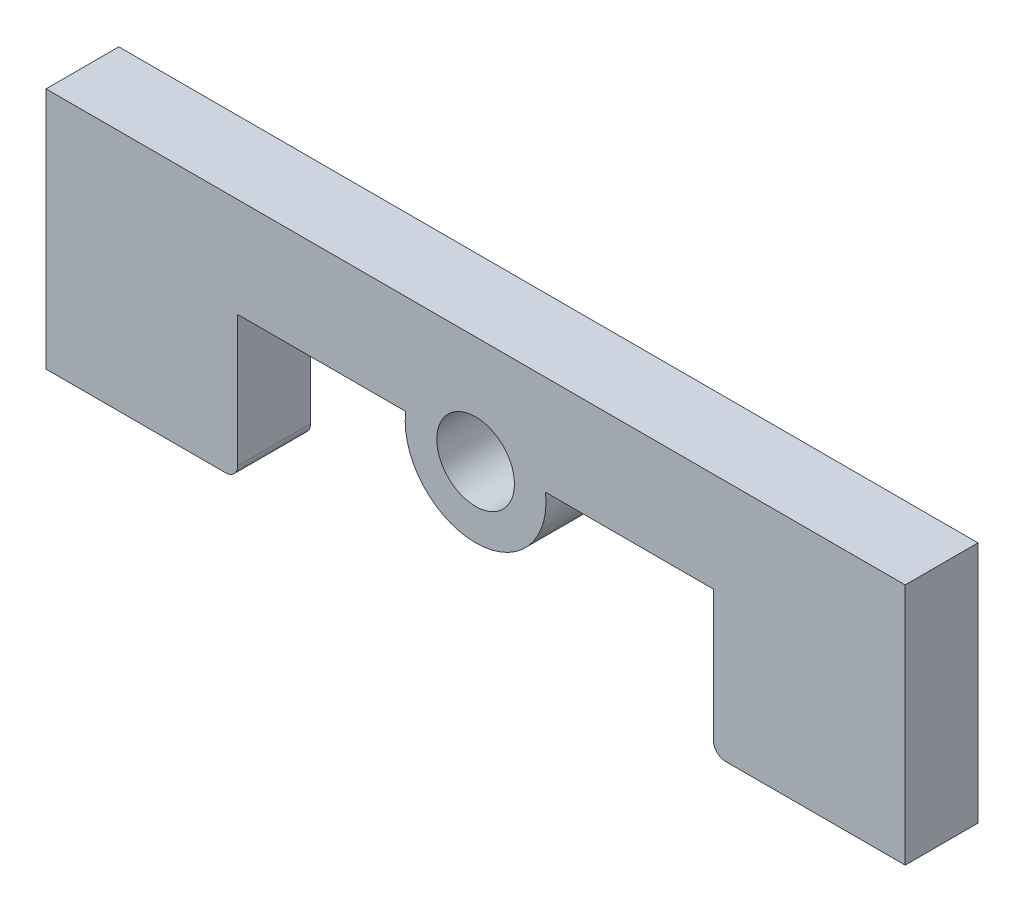
SolidWorks part; units mm, degrees
ref_plane "Front Plane" through (0, 0, 0) normal (0, 0, 1) x (1, 0, 0)
ref_plane "Top Plane" through (0, 0, 0) normal (0, 1, 0) x (1, 0, 0)
ref_plane "Right Plane" through (0, 0, 0) normal (1, 0, 0) x (0, 0, -1)
sketch "Sketch2" plane through (0, 0, 0) normal (0, 0, 1) x (1, 0, 0)
  line L0 (9.8, -5) -> (17.7, -5)
  line L1 (-17.7, -5) -> (-9.8, -5)
  line L2 (-17.7, -5) -> (-17.7, 5)
  line L3 (-17.7, 5) -> (17.7, 5)
  line L4 (17.7, -5) -> (17.7, 5)
  line L5 (-17.7, -5) -> (17.7, 5) construction
  line L6 (-17.7, 5) -> (17.7, -5) construction
  line L8 (-9.8, -5) -> (-9.8, 0.9)
  line L9 (-9.8, 0.9) -> (9.8, 0.9)
  line L10 (9.8, -5) -> (9.8, 0.9)
  circle A0 centre (0, 0.55) radius 1.6
  circle A1 centre (0, 0.55) radius 2.9
  point P0 (0, 0)
  dimension "D3" = 3.2
  dimension "D4" = 4.45
  dimension "D8" = 17.7
  dimension "D9" = 5.8
  dimension "D10" = 4.45
  dimension "D1" = 10
  dimension "D2" = 35.4
  dimension "D5" = 5.9
  dimension "D6" = 19.6
  dimension "D7" = 7.9
extrude "Boss-Extrude2" add sketch "Sketch2" along normal blind 3 contours L9 A1 A0 | A1 L9 L10 L0 L4 L3 L2 L1 L8 | L9 A1 A0 region at (10.1679, -2.05, 0) region at (2.8283, 0.7213, 0) region at (0, 2.1655, 0)
fillet "Fillet1" radius 2.5 2 edges at (-6.3394, 0.9, 0) (6.3394, 0.9, 0)
fillet "Fillet2" radius 0.5 2 edges at (9.8, -5, 1.5) (-9.8, -5, 1.5)
